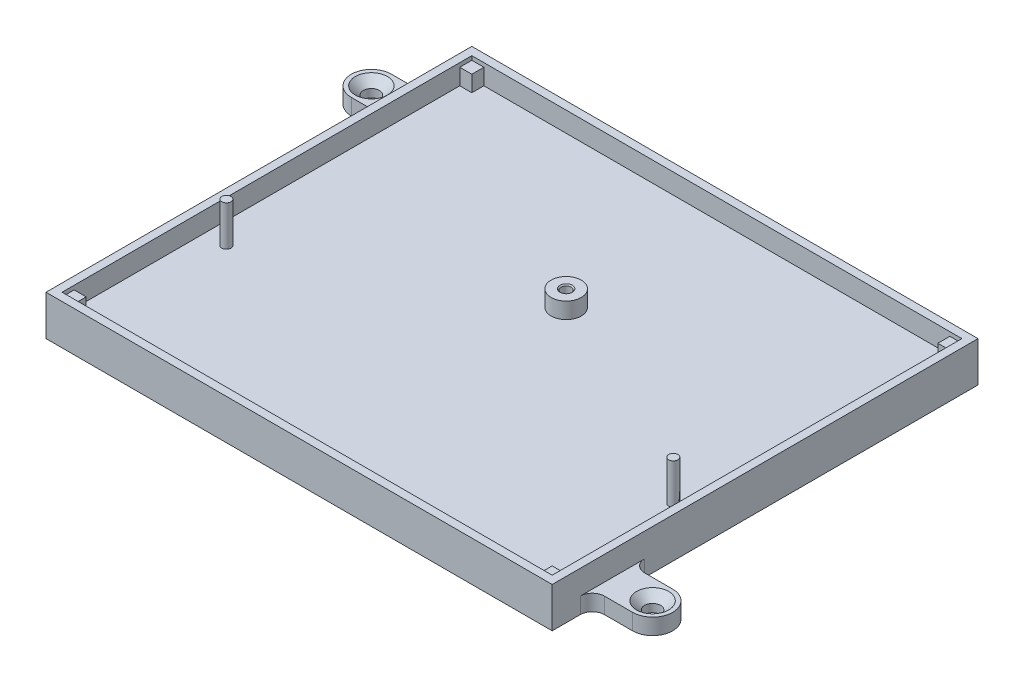
SolidWorks part; units mm, degrees
ref_plane "Front Plane" through (0, 0, 0) normal (0, 0, 1) x (1, 0, 0)
ref_plane "Top Plane" through (0, 0, 0) normal (0, 1, 0) x (1, 0, 0)
ref_plane "Right Plane" through (0, 0, 0) normal (1, 0, 0) x (0, 0, -1)
sketch "Sketch1" plane through (0, 0, 0) normal (0, 1, 0) x (1, 0, 0)
  line L1 (63, 53) -> (-63, 53)
  line L2 (63, 53) -> (63, -53)
  line L3 (63, -53) -> (-63, -53)
  line L4 (-63, 53) -> (-63, -53)
  line L5 (63, 53) -> (-63, -53) construction
  line L6 (63, -53) -> (-63, 53) construction
  point P0 (0, 0)
  dimension "D1" = 106
  dimension "D2" = 126
extrude "Boss-Extrude1" add sketch "Sketch1" along normal blind 5
sketch "Sketch3" plane through (0, 5, 0) normal (0, 1, 0) x (1, 0, 0)
  line L0 (-63, 53) -> (63, 53)
  line L1 (63, 53) -> (63, -53)
  line L2 (63, -53) -> (-63, -53)
  line L3 (-63, -53) -> (-63, 53)
  line L5 (61, -51) -> (-61, -51)
  line L6 (61, -51) -> (61, 51)
  line L7 (61, 51) -> (-61, 51)
  line L8 (-61, -51) -> (-61, 51)
  line L9 (61, -51) -> (-61, 51) construction
  line L10 (61, 51) -> (-61, -51) construction
  point P4 (0, 0)
  dimension "D1" = 2
  dimension "D2" = 2
extrude "Boss-Extrude3" add sketch "Sketch3" along normal blind 5
sketch "Sketch7" plane through (0, 0, 0) normal (0, 1, 0) x (1, 0, 0)
  line L0 (-63, 43) -> (-73, 43)
  line L1 (-63, 53) -> (-63, -53) construction
  line L2 (-73, 33) -> (-63, 33)
  line L3 (-63, 43) -> (-63, 33)
  line L4 (63, -33) -> (73, -33)
  line L5 (63, -53) -> (63, 53) construction
  line L6 (73, -43) -> (63, -43)
  line L7 (63, -43) -> (63, -33)
  line L8 (-63, -53) -> (63, -53) construction
  arc A0 (-73, 43) -> (-73, 33) centre (-73, 38) ccw
  arc A1 (73, -33) -> (73, -43) centre (73, -38) cw
  dimension "D1" = 10
  dimension "D2" = 10
  dimension "D3" = 10
  dimension "D4" = 10
  dimension "D5" = 10
  dimension "D6" = 10
extrude "Boss-Extrude5" add sketch "Sketch7" along normal blind 4
fillet "Fillet1" radius 3 4 edges at (-63, 2, -33) (-63, 2, -43) (63, 2, 43) (63, 2, 33)
hole_wizard "Ø4.0mm Dowel Hole1" positions "Sketch14" profile "Sketch15" hole size "Ø4.0" standard "ISO" end condition through all
sketch "Sketch14" plane through (0, 4, 0) normal (0, 1, 0) x (1, 0, 0)
  line L0 (-73, 43) -> (-73, 33) construction
  line L1 (73, -33) -> (73, -43) construction
  point P0 (-73, 38)
  point P9 (73, -38)
sketch "Sketch15" plane through (-73, 4, -38) normal (1, 0, 0) x (0, 0, 1)
  line L0 (0, 0) -> (0, 4)
  line L1 (0, 4) -> (2, 4)
  line L2 (2, 4) -> (2, 2)
  line L3 (2, 2) -> (4, 0)
  line L5 (4, 0) -> (0, 0)
  line L6 (-2, 2) -> (-4, 0) construction
  line L11 (0, -6.35) -> (0, 107.95) construction
  dimension "Thru Hole Dia." = 4
  dimension "Thru Hole Depth" = 4
  dimension "Near C'Sink Dia." = 8
  dimension "Near C'Sink Angle" = 90
sketch "Sketch17" plane through (0, 5, 0) normal (0, 1, 0) x (1, 0, 0)
  line L0 (-61, -51) -> (61, -51) construction
  line L2 (0, 0) -> (0, 21.9382) construction
  circle A0 centre (-55.626, -15.47) radius 1.15
  circle A1 centre (55.626, -15.47) radius 1.15
  dimension "D1" = 2.3
  dimension "D2" = 35.53
  dimension "D3" = 111.252
extrude "Boss-Extrude6" add sketch "Sketch17" along normal blind 10
sketch "Sketch4" plane through (0, 5, 0) normal (0, 1, 0) x (1, 0, 0)
  line L2 (0, 0) -> (0, 24.1725) construction
  circle A0 centre (0, 13.486) radius 3.75
  circle A1 centre (55.626, -15.47) radius 1.15 construction
  dimension "D1" = 7.5
  dimension "D2" = 28.956
sketch "Sketch18" plane through (0, 5, 0) normal (0, 1, 0) x (1, 0, 0)
  line L0 (0, 0) -> (0, 5.1135) construction
  line L1 (-61, 51) -> (-58, 51)
  line L2 (-61, 51) -> (-61, 48)
  line L3 (-61, 48) -> (-58, 48)
  line L4 (-58, 51) -> (-58, 48)
  line L5 (0, 0) -> (0, 24.1725) construction
  line L6 (58, 51) -> (58, 48)
  line L7 (61, 48) -> (58, 48)
  line L8 (61, 51) -> (61, 48)
  line L9 (61, 51) -> (58, 51)
  line L10 (0, 0) -> (9.5518, 0) construction
  line L11 (-58, -51) -> (-58, -48)
  line L12 (-61, -48) -> (-58, -48)
  line L13 (-61, -51) -> (-61, -48)
  line L14 (-61, -51) -> (-58, -51)
  line L15 (61, -51) -> (58, -51)
  line L16 (61, -51) -> (61, -48)
  line L17 (61, -48) -> (58, -48)
  line L18 (58, -51) -> (58, -48)
  dimension "D1" = 3
  dimension "D2" = 3
extrude "Boss-Extrude7" add sketch "Sketch18" along normal blind 4
extrude "Boss-Extrude8" add sketch "Sketch4" along normal blind 4
hole_wizard "M3 Tapped Hole1" positions "Sketch19" profile "Sketch20" tap size "M3" standard "ISO" end condition through all
sketch "Sketch19" plane through (0, 9, 0) normal (0, 1, 0) x (1, 0, 0)
  point P0 (0, 13.486)
sketch "Sketch20" plane through (0, 9, -13.486) normal (1, 0, 0) x (0, 0, 1)
  line L0 (0, 0) -> (0, 9)
  line L1 (0, 9) -> (1.25, 9)
  line L2 (1.25, 9) -> (1.25, 0.275)
  line L3 (1.25, 0.275) -> (1.525, 0)
  line L5 (1.525, 0) -> (0, 0)
  line L6 (-1.25, 0.275) -> (-1.525, 0) construction
  line L11 (0, -6.35) -> (0, 107.95) construction
  dimension "Thru Tap Drill Dia." = 2.5
  dimension "Thru Tap Drill Depth" = 9
  dimension "Near C'Sink Dia." = 3.05
  dimension "Near C'Sink Angle" = 90
cosmetic thread "Hole Thread1" parameters "D2"=3
